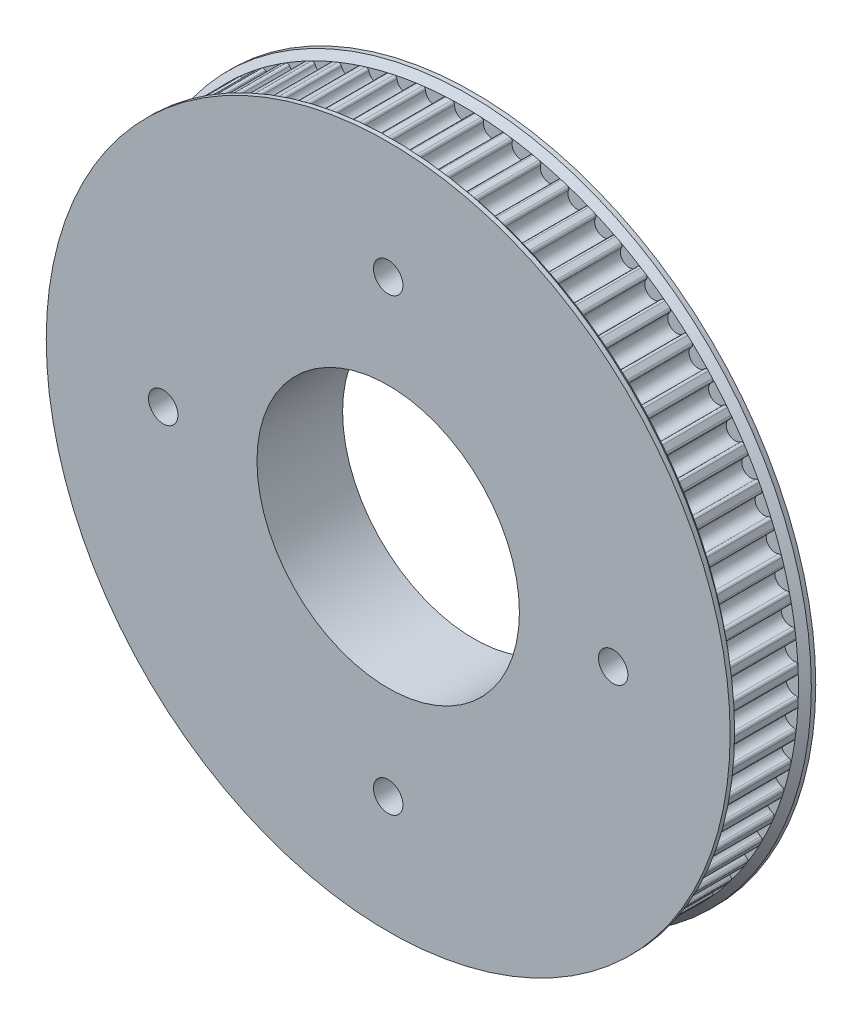
SolidWorks part; units mm, degrees
material "Nailon 6/10"
ref_plane "Alzado" through (0, 0, 0) normal (0, 0, 1) x (1, 0, 0)
ref_plane "Planta" through (0, 0, 0) normal (0, 1, 0) x (1, 0, 0)
ref_plane "Vista lateral" through (0, 0, 0) normal (1, 0, 0) x (0, 0, -1)
sketch "Croquis2" plane through (0, 0, 0) normal (0, 0, 1) x (1, 0, 0)
  circle A0 centre (0, 0) radius 56.7243
  dimension "D1" = 113.4486
extrude "Saliente-Extruir1" add sketch "Croquis2" along normal mid plane 11
sketch "Croquis4" plane through (0, 0, 0) normal (0, 0, 1) x (1, 0, 0)
  line L0 (0, 0) -> (0, 56.1893) construction
  line L1 (0, 0) -> (4.8972, 55.9755) construction
  circle A0 centre (0, 0) radius 54.6643
  circle A1 centre (0, 56.1893) radius 1.525 construction
  circle A2 centre (4.8972, 55.9755) radius 1.525 construction
  circle A3 centre (1.9537, 56.2604) radius 0.43 construction
  circle A4 centre (0, 0) radius 56.7243 construction
  circle A5 centre (2.9571, 56.2166) radius 0.43 construction
  arc A6 (-1.524, 56.2447) -> (1.524, 56.2447) centre (0, 56.1893) ccw
  arc A7 (1.524, 56.2447) -> (1.9686, 56.6901) centre (1.9537, 56.2604) cw
  arc A8 (2.9797, 56.646) -> (1.9686, 56.6901) centre (0, 0) ccw
  arc A9 (2.9797, 56.646) -> (3.3839, 56.1635) centre (2.9571, 56.2166) cw
  arc A10 (3.3839, 56.1635) -> (4.7643, 54.4563) centre (4.8972, 55.9755) ccw
  arc A11 (-3.3839, 56.1635) -> (-4.7643, 54.4563) centre (-4.8972, 55.9755) cw
  arc A12 (-2.9797, 56.646) -> (-3.3839, 56.1635) centre (-2.9571, 56.2166) ccw
  arc A13 (-2.9797, 56.646) -> (-1.9686, 56.6901) centre (0, 0) cw
  arc A14 (-1.524, 56.2447) -> (-1.9686, 56.6901) centre (-1.9537, 56.2604) ccw
  arc A15 (-1.9686, 56.6901) -> (1.9686, 56.6901) centre (0, 0) cw
  dimension "D1" = 109.3286
  dimension "D3" = 3.05
  dimension "D4" = 0.86
  dimension "D2" = 5
extrude "Cortar-Extruir2" cut sketch "Croquis4" against normal through all both and the other way through all contours A15 A14 A6 A7 region at (0, 55.8333, 0)
pattern_circular "MatrizC4" count 72 over 360 about axis through (0, 0, 5.5) along (0, 0, -1) of "Cortar-Extruir2"
sketch "Croquis5" plane through (0, 0, 0) normal (0, 1, 0) x (1, 0, 0)
  line L0 (0, 0) -> (0, 5.5) construction
  line L1 (1.525, 5.5) -> (-1.525, 5.5) construction
  line L2 (0, 5.5) -> (56.7243, 5.5)
  line L3 (56.7243, 5.5) -> (57.916, 6.5)
  line L4 (57.916, 6.5) -> (57.916, 7.25)
  line L5 (57.916, 7.25) -> (0, 7.25)
  line L6 (0, 7.25) -> (0, 5.5)
  line L7 (0, 0) -> (56.7243, 0) construction
  line L9 (0, -7.25) -> (0, -5.5)
  line L10 (57.916, -7.25) -> (0, -7.25)
  line L11 (57.916, -6.5) -> (57.916, -7.25)
  line L12 (56.7243, -5.5) -> (57.916, -6.5)
  line L13 (0, -5.5) -> (56.7243, -5.5)
  dimension "D1" = 50
  dimension "D2" = 1.75
  dimension "D3" = 0.75
  dimension "D4" = 113.4486
revolve "Revolución1" add sketch "Croquis5" angle 360 about L0
sketch "Croquis6" plane through (0, 0, 0) normal (0, 0, 1) x (1, 0, 0)
  line L1 (3.6882, -6.3881) -> (7.3763, 0)
  line L2 (7.3763, 0) -> (3.6882, 6.3881)
  line L3 (3.6882, 6.3881) -> (-2.9954, 6.3881)
  line L4 (-4.0346, 5.7881) -> (-7.3763, 0)
  line L5 (-7.3763, 0) -> (-3.6882, -6.3881)
  line L6 (-3.6882, -6.3881) -> (3.6882, -6.3881)
  line L7 (-3.6882, 6.3881) -> (-7.3763, 0)
  line L8 (-7.3763, 0) -> (-3.6882, -6.3881)
  line L9 (-3.6882, -6.3881) -> (3.6882, -6.3881)
  line L10 (3.6882, -6.3881) -> (7.3763, 0)
  line L11 (7.3763, 0) -> (3.6882, 6.3881)
  line L12 (3.6882, 6.3881) -> (-3.6882, 6.3881)
  circle A0 centre (0, 0) radius 6.3881 construction
  arc A1 (-3.3418, 6.5881) -> (-4.0346, 6.1881) centre (-3.6882, 6.3881) ccw
  arc A2 (-4.0346, 5.7881) -> (-4.0346, 6.1881) centre (-4.381, 5.9881) ccw
  arc A3 (-2.9954, 6.3881) -> (-3.3418, 6.5881) centre (-2.9954, 6.7881) cw
  circle A4 centre (0, 0) radius 6.3881 construction
  arc A5 (4.0346, 5.7881) -> (4.0346, 6.1881) centre (4.381, 5.9881) cw
  arc A6 (4.0346, 6.1881) -> (3.3418, 6.5881) centre (3.6882, 6.3881) ccw
  arc A7 (2.9954, 6.3881) -> (3.3418, 6.5881) centre (2.9954, 6.7881) ccw
  arc A8 (7.0299, -0.6) -> (7.3763, -0.4) centre (7.3763, -0.8) cw
  arc A9 (7.3763, -0.4) -> (7.3763, 0.4) centre (7.3763, 0) ccw
  arc A10 (7.0299, 0.6) -> (7.3763, 0.4) centre (7.3763, 0.8) ccw
  arc A11 (2.9954, -6.3881) -> (3.3418, -6.5881) centre (2.9954, -6.7881) cw
  arc A12 (3.3418, -6.5881) -> (4.0346, -6.1881) centre (3.6882, -6.3881) ccw
  arc A13 (4.0346, -5.7881) -> (4.0346, -6.1881) centre (4.381, -5.9881) ccw
  arc A14 (-4.0346, -5.7881) -> (-4.0346, -6.1881) centre (-4.381, -5.9881) cw
  arc A15 (-4.0346, -6.1881) -> (-3.3418, -6.5881) centre (-3.6882, -6.3881) ccw
  arc A16 (-2.9954, -6.3881) -> (-3.3418, -6.5881) centre (-2.9954, -6.7881) ccw
  arc A17 (-7.0299, 0.6) -> (-7.3763, 0.4) centre (-7.3763, 0.8) cw
  arc A18 (-7.3763, 0.4) -> (-7.3763, -0.4) centre (-7.3763, 0) ccw
  arc A19 (-7.0299, -0.6) -> (-7.3763, -0.4) centre (-7.3763, -0.8) ccw
  point P54 (0, 0)
  dimension "D1" = 12.7762
  dimension "D2" = 0.8
  dimension "D3" = 0.4
  dimension "D4" = 0.4
  dimension "D5" = 6
extrude "Cortar-Extruir3" cut sketch "Croquis6" against normal through all both and the other way through all contours L3 L12 L7 L4 L5 L8 L6 L9 L1 L10 L2 L11 | A7 L3 L11 A5 A6 | L12 A3 A1 A2 L7 | A19 L5 L7 A17 A18 | A16 L6 L8 A14 A15 | A13 L1 L9 A11 A12 | A10 L2 L10 A8 A9 region at (0, 0, 0) region at (3.7325, -6.4649, 0) region at (7.465, 0, 0) region at (-3.7325, -6.4649, 0) region at (3.7325, 6.4649, 0) region at (-7.465, 0, 0) region at (-3.7325, 6.4649, 0)
sketch "Croquis7" plane through (0, 0, 7.25) normal (0, 0, 1) x (1, 0, 0)
  line L0 (0, 0) -> (0, 38.1) construction
  line L1 (0, 0) -> (0, 38.1) construction
  circle A0 centre (0, 38.1) radius 2.4892
  circle A1 centre (0, 0) radius 22.225
  circle A2 centre (38.1, 0) radius 2.4892
  circle A3 centre (0, -38.1) radius 2.4892
  circle A4 centre (-38.1, 0) radius 2.4892
  dimension "D1" = 4.9784
  dimension "D3" = 44.45
  dimension "D2" = 38.1
  dimension "D5" = 38.1
  dimension "D4" = 4
extrude "Cortar-Extruir4" cut sketch "Croquis7" against normal up to surface (14.5 mm away) up to face at (57.916, 0, -7.25)
equation "\"X\"= \"DimCal\""
equation "\"Y\"= \"X\" - ( 2 * 2.06 )"
equation "\"Nt\"= 72'Numero de dientes ( Minimo 10 reco 18)"
equation "\"A\"= 360° / \"Nt\""
equation "\"G\"= 11mm"
equation "\"D1@Croquis2\"=\"X\""
equation "\"D1@Saliente-Extruir1\"=\"G\""
equation "\"D1@Croquis4\"=\"Y\""
equation "\"D2@Croquis4\"=\"A\""
equation "\"D1@MatrizC4\"=\"Nt\""
equation "\"TP\"= 5mm'Tooth pitch"
equation "\"PLO\"= 0.5715mm'Pitch line offset"
equation "\"DimCal\"= 2 * ( ( \"Nt\" * \"TP\" ) / ( pi * 2 ) - \"PLO\" )'Diameter (calculated)"
equation "\"D4@Croquis5\"=\"X\""
